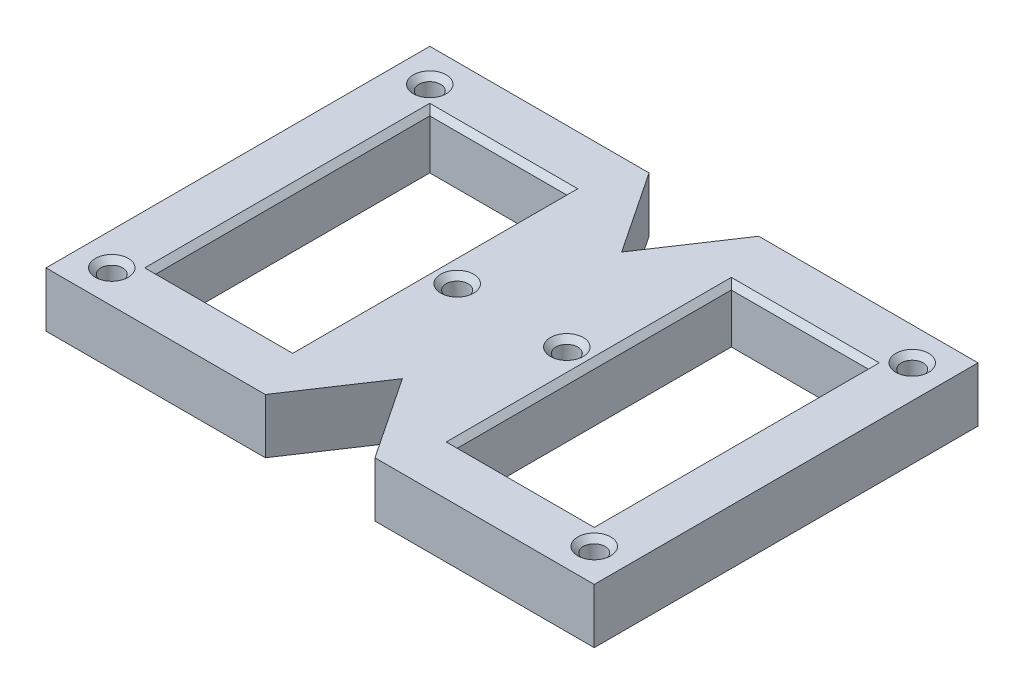
SolidWorks part; units mm, degrees
ref_plane "Alzado" through (0, 0, 0) normal (0, 0, 1) x (1, 0, 0)
ref_plane "Planta" through (0, 0, 0) normal (0, 1, 0) x (1, 0, 0)
ref_plane "Vista lateral" through (0, 0, 0) normal (1, 0, 0) x (0, 0, -1)
sketch "Croquis1" plane through (0, 0, 0) normal (0, 1, 0) x (1, 0, 0)
  line L1 (50, -35) -> (-50, -35)
  line L2 (50, -35) -> (50, 35)
  line L3 (50, 35) -> (-50, 35)
  line L4 (-50, -35) -> (-50, 35)
  line L5 (50, -35) -> (-50, 35) construction
  line L6 (50, 35) -> (-50, -35) construction
  point P0 (0, 0)
  dimension "D1" = 100
  dimension "D2" = 70
extrude "Saliente-Extruir1" add sketch "Croquis1" along normal blind 10
sketch "Croquis3" plane through (0, 10, 0) normal (0, 1, 0) x (1, 0, 0)
  line L0 (50, 35) -> (-50, 35) construction
  line L1 (-44, -29) -> (44, -29) construction
  line L2 (-44, -29) -> (-44, 29) construction
  line L3 (-44, 29) -> (44, 29) construction
  line L4 (44, -29) -> (44, 29) construction
  line L5 (-44, -29) -> (44, 29) construction
  line L6 (-44, 29) -> (44, -29) construction
  line L7 (-50, 35) -> (-50, -35) construction
  circle A0 centre (-44, 29) radius 2
  circle A1 centre (44, 29) radius 2
  circle A2 centre (44, -29) radius 2
  circle A3 centre (-44, -29) radius 2
  point P0 (0, 0)
  dimension "D1" = 4
  dimension "D2" = 6
  dimension "D3" = 6
extrude "Cortar-Extruir2" cut sketch "Croquis3" against normal through all
sketch "Croquis6" plane through (0, 10, 0) normal (0, 1, 0) x (1, 0, 0)
  line L0 (-10, 0) -> (10, 0) construction
  circle A0 centre (-10, 0) radius 2
  circle A1 centre (10, 0) radius 2
  circle A2 centre (-44, 29) radius 2 construction
  dimension "D1" = 10
  dimension "D2" = 10
extrude "Cortar-Extruir3" cut sketch "Croquis6" against normal through all
sketch "Croquis7" plane through (0, 0, 0) normal (0, -1, 0) x (1, 0, 0)
  line L1 (-40, -25) -> (-15, -25)
  line L2 (-40, -25) -> (-40, 25)
  line L3 (-40, 25) -> (-15, 25)
  line L4 (-15, -25) -> (-15, 25)
  line L5 (-40, -25) -> (-15, 25) construction
  line L6 (-40, 25) -> (-15, -25) construction
  line L10 (15, -25) -> (40, -25)
  line L11 (15, -25) -> (15, 25)
  line L12 (15, 25) -> (40, 25)
  line L13 (40, -25) -> (40, 25)
  line L14 (15, -25) -> (40, 25) construction
  line L15 (15, 25) -> (40, -25) construction
  point P0 (-27.5, 0)
  point P7 (27.5, 0)
  dimension "D1" = 15
  dimension "D2" = 15
  dimension "D3" = 40
  dimension "D4" = 40
  dimension "D5" = 25
  dimension "D6" = 25
extrude "Cortar-Extruir4" cut sketch "Croquis7" against normal through all
sketch "Croquis8" plane through (0, 10, 0) normal (0, 1, 0) x (1, 0, 0)
  line L0 (-10, 35) -> (0, 20)
  line L1 (50, 35) -> (-50, 35) construction
  line L2 (0, 20) -> (10, 35)
  line L4 (-10, 35) -> (10, 35)
  line L6 (-10, 0) -> (10, 0) construction
  point P4 (0, 35)
  point P14 (0, 0)
  dimension "D1" = 20
  dimension "D2" = 20
extrude "Cortar-Extruir5" cut sketch "Croquis8" against normal through all
mirror "Simetría1" about plane through (0, 0, 0) normal (0, 0, 1) of "Cortar-Extruir5"
chamfer "Chaflán1" distance 1 angle 45 14 edges at (44, 10, 31) (44, 10, -27) (10, 10, 2) (-10, 10, 2) (-44, 10, 31) (-44, 10, -27) (27.5, 10, 25) (40, 10, 0) (15, 10, 0) (27.5, 10, -25) (-27.5, 10, 25) (-15, 10, 0) (-27.5, 10, -25) (-40, 10, 0)
